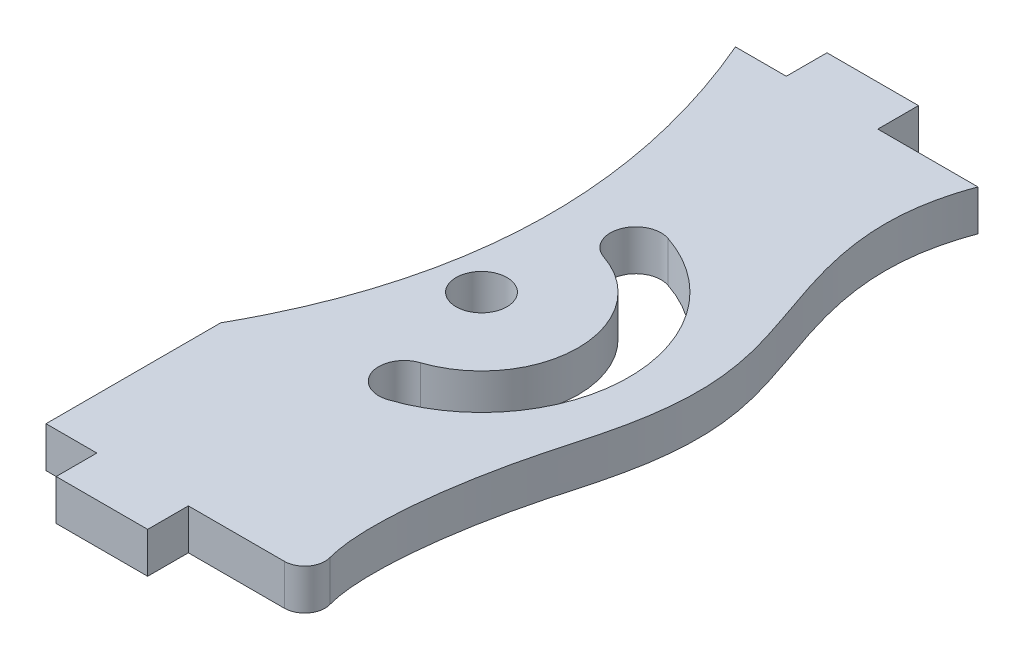
SolidWorks part; units mm, degrees
other "Marca1"
sketch "Croquis2"
ref_plane "Alzado" through (0, 0, 0) normal (0, 0, 1) x (1, 0, 0)
ref_plane "Planta" through (0, 0, 0) normal (0, 1, 0) x (1, 0, 0)
ref_plane "Vista lateral" through (0, 0, 0) normal (1, 0, 0) x (0, 0, -1)
sketch "Croquis1" plane through (0, 0, 0) normal (0, 1, 0) x (1, 0, 0)
  line L0 (-29.8355, 18.6892) -> (3.5276, 18.6892) construction
  line L1 (2.715, 0) -> (2.715, 2.0882) construction
  line L3 (-0.3831, 0.651) -> (0.3831, 0.651)
  line L4 (-0.3831, 0.651) -> (-0.3831, -0.651)
  line L5 (-0.3831, -0.651) -> (0.3831, -0.651)
  line L6 (0.3831, 0.651) -> (0.3831, -0.651)
  line L7 (-0.3831, 0.651) -> (0.3831, -0.651) construction
  line L8 (-0.3831, -0.651) -> (0.3831, 0.651) construction
  line L10 (-4.2005, 16.6892) -> (-1.7005, 16.6892)
  line L11 (-1.7005, 16.6892) -> (-1.7005, 18.6892)
  line L12 (-1.7005, 18.6892) -> (2.7995, 18.6892)
  line L13 (2.7995, 18.6892) -> (2.7995, 16.6892)
  line L14 (2.7995, 16.6892) -> (7.7266, 16.6892)
  line L16 (-21.2785, 20.7575) -> (-21.2785, -9.2425) construction
  line L17 (1.8937, -16.3108) -> (6.6151, -16.3108)
  line L18 (1.8937, -18.3108) -> (1.8937, -16.3108)
  line L19 (-2.6063, -18.3108) -> (1.8937, -18.3108)
  line L20 (-2.6063, -16.3108) -> (-2.6063, -18.3108)
  line L21 (-5.1063, -16.3108) -> (-2.6063, -16.3108)
  line L22 (-5.1063, -7.7189) -> (-5.1063, -16.3108)
  circle A0 centre (0, 0) radius 1.25
  arc A3 (4.1833, -4.3012) -> (5.6435, -2.0375) centre (0, 0) ccw
  arc A4 (4.1833, -4.3012) -> (5.6435, -2.0375) centre (0, 0) ccw construction
  arc A10 (6.6151, -16.3108) -> (7.5777, -15.04) centre (6.6151, -15.3108) ccw
  arc A15 (0.6716, -5.9623) -> (6, 0) centre (0, 0) ccw
  arc A17 (1.8924, 5.6937) -> (0.6716, 5.9623) centre (0, 0) ccw
  arc A18 (1.8924, -5.6937) -> (6, 0) centre (0, 0) ccw construction
  arc A19 (2.2867, -6.8799) -> (2.2867, 6.8799) centre (0, 0) ccw
  arc A20 (1.4982, -4.5075) -> (1.4982, 4.5075) centre (0, 0) ccw
  arc A21 (1.4982, -4.5075) -> (2.2867, -6.8799) centre (1.8924, -5.6937) ccw
  arc A22 (2.2867, 6.8799) -> (1.4982, 4.5075) centre (1.8924, 5.6937) ccw
  arc A23 (0.6716, -5.9623) -> (6, 0) centre (0, 0) ccw
  arc A24 (1.8924, 5.6937) -> (0.6716, 5.9623) centre (0, 0) ccw
  spline S0 degree 3 poles (7.5777, -15.04) (7.0091, -13.0184) (7.4797, -8.2818) (9.8371, -0.2699) (9.5069, 5.6257) (5.8998, 11.8316) (7.7266, 16.6892) knots 0.078668 0.078668 0.078668 0.078668 0.337938 0.393993 0.63921 1 1 1 1
  spline S1 degree 2 poles (-4.2005, 16.6892) (1.3277, 3.7559) (-5.1063, -7.7189) knots 0 0 0 1 1 1
  point P12 (6, 0)
  point P15 (4.1833, -4.3012)
  point P26 (-5.2403, 2.9223)
  dimension "D1" = 2.5
  dimension "D3" = 1
  dimension "D4" = 30
  dimension "D2" = 12
  dimension "D5" = 2
  dimension "D6" = 4.5
  dimension "D7" = 2.5
  dimension "D8" = 2
  dimension "D9" = 2.5
  dimension "D10" = 4.5
extrude "Saliente-Extruir1" add sketch "Croquis1" along normal blind 2 contours L17 S0 L14 L13 L12 L11 L10 L22 L21 L20 L19 L18 A0 A20 region at (2.0442, 0, 0.6635)
